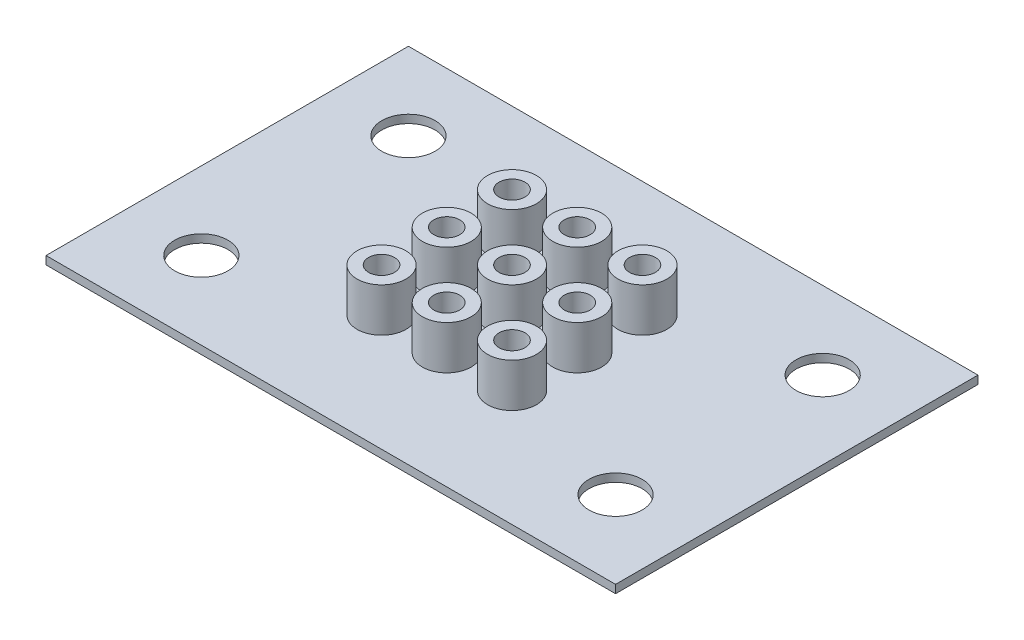
SolidWorks part; units mm, degrees
ref_plane "Front Plane" through (0, 0, 0) normal (0, 0, 1) x (1, 0, 0)
ref_plane "Top Plane" through (0, 0, 0) normal (0, 1, 0) x (1, 0, 0)
ref_plane "Right Plane" through (0, 0, 0) normal (1, 0, 0) x (0, 0, -1)
sketch "Sketch1" plane through (0, 0, 0) normal (0, 1, 0) x (1, 0, 0)
  line L0 (9.525, 34.925) -> (0, 34.925) construction
  line L1 (0, 0) -> (69.85, 0)
  line L2 (0, 0) -> (0, 44.45)
  line L3 (0, 44.45) -> (69.85, 44.45)
  line L4 (69.85, 0) -> (69.85, 44.45)
  line L5 (9.525, 34.925) -> (60.325, 34.925) construction
  line L6 (9.525, 34.925) -> (9.525, 9.525) construction
  line L7 (9.525, 9.525) -> (60.325, 9.525) construction
  line L8 (60.325, 34.925) -> (60.325, 9.525) construction
  line L9 (9.525, 34.925) -> (9.525, 44.45) construction
  line L10 (34.925, 22.225) -> (34.925, 30.225) construction
  circle A0 centre (9.525, 34.925) radius 3.2639
  circle A1 centre (60.325, 34.925) radius 3.2639
  circle A2 centre (9.525, 9.525) radius 3.2639
  circle A3 centre (60.325, 9.525) radius 3.2639
  circle A4 centre (34.925, 22.225) radius 1.25
  circle A5 centre (42.925, 22.225) radius 1.25
  circle A6 centre (42.925, 30.225) radius 1.25
  circle A7 centre (34.925, 30.225) radius 1.25
  circle A8 centre (26.925, 22.225) radius 1.25
  circle A9 centre (26.925, 30.225) radius 1.25
  circle A10 centre (34.925, 30.225) radius 1.25
  circle A11 centre (42.925, 22.225) radius 1.25
  circle A12 centre (42.925, 14.225) radius 1.25
  circle A13 centre (34.925, 14.225) radius 1.25
  circle A14 centre (26.925, 22.225) radius 1.25
  circle A15 centre (26.925, 14.225) radius 1.25
  circle A16 centre (34.925, 14.225) radius 1.25
  point P13 (34.925, 34.925)
  point P14 (34.925, 44.45)
  point P20 (69.85, 22.225)
  dimension "D5" = 6.5278
  dimension "D6" = 2.5
  dimension "D1" = 69.85
  dimension "D2" = 44.45
  dimension "D3" = 50.8
  dimension "D4" = 25.4
  dimension "D9" = 8
  dimension "D7" = 2
  dimension "D8" = 2
  dimension "D10" = 2
  dimension "D11" = 2
  dimension "D12" = 2
  dimension "D13" = 2
  dimension "D14" = 2
  dimension "D15" = 2
extrude "Boss-Extrude1" add sketch "Sketch1" along normal blind 1 contours L1 L4 L3 L2 A15 A13 A12 A9 A8 A7 A6 A5 A4 A3 A2 A1 A0 region at (0.8279, 0, -22.225)
sketch "Sketch2" plane through (0, 1, 0) normal (0, 1, 0) x (1, 0, 0)
  line L0 (34.925, 22.225) -> (34.925, 30.225) construction
  circle A0 centre (34.925, 22.225) radius 3
  circle A1 centre (34.925, 22.225) radius 1.59
  circle A2 centre (42.925, 22.225) radius 3
  circle A3 centre (42.925, 22.225) radius 1.59
  circle A4 centre (42.925, 30.225) radius 3
  circle A5 centre (42.925, 30.225) radius 1.59
  circle A6 centre (34.925, 30.225) radius 3
  circle A7 centre (34.925, 30.225) radius 1.59
  circle A8 centre (42.925, 22.225) radius 1.59
  circle A9 centre (42.925, 22.225) radius 3
  circle A10 centre (42.925, 14.225) radius 1.59
  circle A11 centre (42.925, 14.225) radius 3
  circle A12 centre (34.925, 14.225) radius 1.59
  circle A13 centre (34.925, 14.225) radius 3
  circle A14 centre (26.925, 22.225) radius 3
  circle A15 centre (26.925, 22.225) radius 1.59
  circle A16 centre (26.925, 30.225) radius 3
  circle A17 centre (26.925, 30.225) radius 1.59
  circle A18 centre (34.925, 30.225) radius 3
  circle A19 centre (34.925, 30.225) radius 1.59
  circle A20 centre (26.925, 22.225) radius 1.59
  circle A21 centre (26.925, 22.225) radius 3
  circle A22 centre (26.925, 14.225) radius 1.59
  circle A23 centre (26.925, 14.225) radius 3
  circle A24 centre (34.925, 14.225) radius 1.59
  circle A25 centre (34.925, 14.225) radius 3
  dimension "D1" = 3.18
  dimension "D2" = 6
  dimension "D5" = 8
  dimension "D3" = 2
  dimension "D4" = 2
  dimension "D6" = 2
  dimension "D7" = 2
  dimension "D8" = 2
  dimension "D9" = 2
extrude "Boss-Extrude2" add sketch "Sketch2" along normal blind 5.35 contours A16 A17 | A14 A15 | A6 A7 | A4 A5 | A2 A3 | A1 A0 | A23 A22 | A13 A12 | A11 A10 region at (32.0099, 1, -22.225) region at (40.0099, 1, -22.225) region at (40.0099, 1, -30.225) region at (32.0099, 1, -30.225) region at (40.0099, 1, -14.225) region at (32.0099, 1, -14.225) region at (24.0099, 1, -22.225) region at (24.0099, 1, -30.225) region at (24.0099, 1, -14.225)
